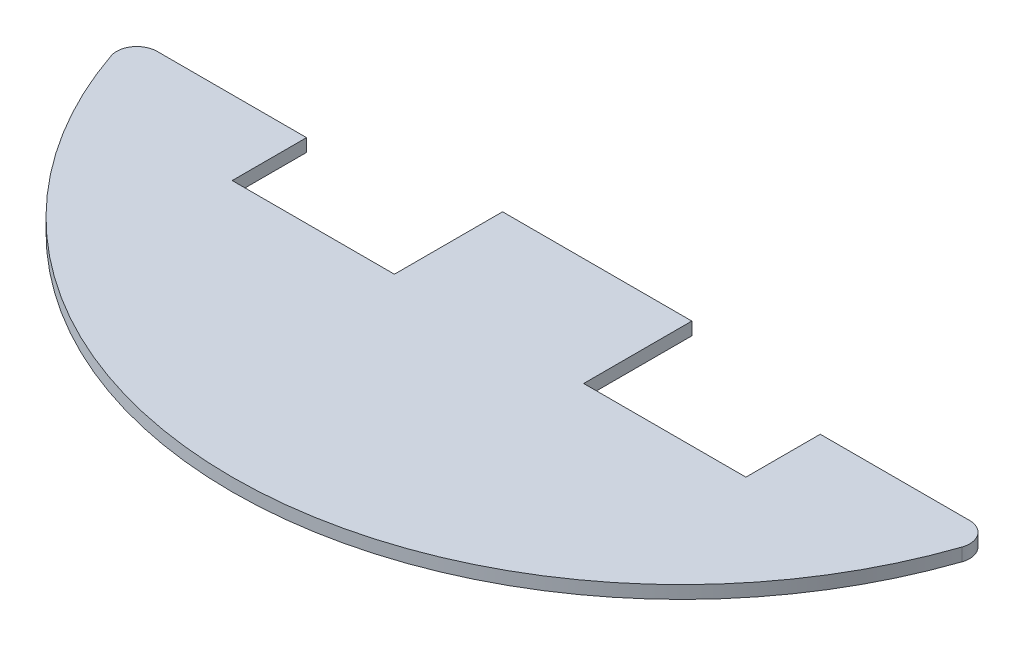
SolidWorks part; units mm, degrees
material "ABS"
ref_plane "Front Plane" through (0, 0, 0) normal (0, 0, 1) x (1, 0, 0)
ref_plane "Top Plane" through (0, 0, 0) normal (0, 1, 0) x (1, 0, 0)
ref_plane "Right Plane" through (0, 0, 0) normal (1, 0, 0) x (0, 0, -1)
sketch "Sketch1" plane through (0, 0, 0) normal (0, 1, 0) x (1, 0, 0)
  line L1 (-18, -10) -> (18, -10)
  line L2 (-18, -10) -> (-18, 10)
  line L3 (-18, 10) -> (18, 10)
  line L4 (18, -10) -> (18, 10)
  line L5 (-18, -10) -> (18, 10) construction
  line L6 (-18, 10) -> (18, -10) construction
  point P0 (0, 0)
  dimension "D1" = 36
  dimension "D2" = 20
extrude "Boss-Extrude1" add sketch "Sketch1" along normal blind 1.9
sketch "Sketch2" plane through (0, 0, 0) normal (0, -1, 0) x (1, 0, 0)
  line L0 (0, -10) -> (0, 10) construction
  line L1 (18, -10) -> (-18, -10) construction
  line L2 (-18, 10) -> (18, 10) construction
sketch "Sketch3" plane through (0, 0, 0) normal (0, -1, 0) x (1, 0, 0)
  line L0 (0, 0) -> (0, 54.5743) construction
  line L1 (-38, 43.5743) -> (-38, 54.5743)
  line L2 (-38, 54.5743) -> (-14, 54.5743)
  line L3 (0, 0) -> (0, -36.2287) construction
  line L4 (-14, 54.5743) -> (-14, 38.5743)
  line L5 (-14, 38.5743) -> (14, 38.5743)
  line L6 (14, 38.5743) -> (14, 54.5743)
  line L7 (38, 43.5743) -> (60.0999, 43.5743)
  line L8 (14, 54.5743) -> (38, 54.5743)
  line L9 (-38, 43.5743) -> (-60.0999, 43.5743)
  line L10 (38, 54.5743) -> (38, 43.5743)
  line L11 (-26, -21.0972) -> (-26, 54.5743) construction
  line L12 (-37, -21.0972) -> (-15, -21.0972) construction
  arc A2 (68.1909, 19.5743) -> (-68.1909, 19.5743) centre (0, 26.0743) ccw construction
  arc A3 (62.9393, 47.5428) -> (-62.9393, 47.5428) centre (0, 26.0743) ccw
  circle A4 centre (0, 26.0743) radius 72.5 construction
  arc A5 (-60.0999, 43.5743) -> (-62.9393, 47.5428) centre (-60.0999, 46.5743) cw
  arc A6 (60.0999, 43.5743) -> (62.9393, 47.5428) centre (60.0999, 46.5743) ccw
  point P14 (-26, 54.5743)
  point P20 (-64.1561, 43.5743)
  point P26 (64.1561, 43.5743)
  dimension "D1" = 2
  dimension "D3" = 5
  dimension "D4" = 52
  dimension "D5" = 3
  dimension "D6" = 16
  dimension "D2" = 24
extrude "Boss-Extrude2" add sketch "Sketch3" against normal blind 1.9
sketch "Sketch5" plane through (0, 1.9, 0) normal (0, 1, 0) x (1, 0, 0)
  line L2 (-29.6163, 16.0438) -> (29.6163, 16.0438)
  line L3 (-29.6163, 16.0438) -> (-29.6163, -16.0438)
  line L4 (-29.6163, -16.0438) -> (29.6163, -16.0438)
  line L5 (29.6163, 16.0438) -> (29.6163, -16.0438)
  line L6 (-29.6163, 16.0438) -> (29.6163, -16.0438) construction
  line L7 (-29.6163, -16.0438) -> (29.6163, 16.0438) construction
extrude "Cut-Extrude2" cut sketch "Sketch5" against normal blind 10
sketch "Sketch8" plane through (0, 1.9, 0) normal (0, 1, 0) x (1, 0, 0)
  line L0 (0, -26.0743) -> (-45.6084, -71.6827) construction
  line L1 (0, -26.0743) -> (0, -90.5743) construction
  line L2 (0, -26.0743) -> (-24.6831, -85.6645) construction
  line L3 (-60.0999, -43.5743) -> (-38, -43.5743) construction
  line L4 (0, -26.0743) -> (45.6084, -71.6827) construction
  line L5 (0, -26.0743) -> (24.6831, -85.6645) construction
  circle A0 centre (0, -26.0743) radius 64.5 construction
  dimension "D1" = 45
  dimension "D2" = 67.5
sketch "Sketch9" plane through (0, 1.9, 0) normal (0, 1, 0) x (1, 0, 0)
  line L0 (18.5, -59.5743) -> (11.5, -59.5743)
  line L1 (18.5, -59.5743) -> (18.5, -71.5743)
  line L2 (18.5, -71.5743) -> (11.5, -71.5743)
  line L3 (11.5, -59.5743) -> (11.5, -71.5743)
  line L4 (-11.5, -59.5743) -> (-11.5, -71.5743)
  line L5 (-18.5, -71.5743) -> (-11.5, -71.5743)
  line L6 (-18.5, -59.5743) -> (-18.5, -71.5743)
  line L7 (-18.5, -59.5743) -> (-11.5, -59.5743)
  line L8 (-15, -59.5743) -> (-15, -71.5743) construction
  line L9 (15, -59.5743) -> (15, -71.5743) construction
  line L10 (7, -69.5743) -> (-7, -69.5743) construction
  line L11 (-15, -65.5743) -> (15, -65.5743) construction
  line L12 (0, -26.0743) -> (0, -90.5743) construction
  line L13 (-18.5, -59.5743) -> (18.5, -59.5743) construction
  line L14 (0, -69.5743) -> (0, -59.5743) construction
  line L15 (-18.5, -59.5743) -> (-11.5, -71.5743)
  line L16 (-18.5, -71.5743) -> (-11.5, -59.5743)
  line L17 (11.5, -59.5743) -> (18.5, -71.5743)
  line L18 (18.5, -59.5743) -> (11.5, -71.5743)
  circle A0 centre (7, -69.5743) radius 1.75
  circle A1 centre (-7, -69.5743) radius 1.75
  circle A2 centre (0, -61.0743) radius 1.75
  point P16 (0, -69.5743)
  point P17 (0, -65.5743)
  point P28 (-15, -65.5743)
  point P29 (15, -65.5743)
  dimension "D4" = 3.5
  dimension "D8" = 10.5
  dimension "D1" = 7
  dimension "D2" = 12
  dimension "D3" = 30
  dimension "D5" = 14
  dimension "D6" = 2
  dimension "D7" = 25
